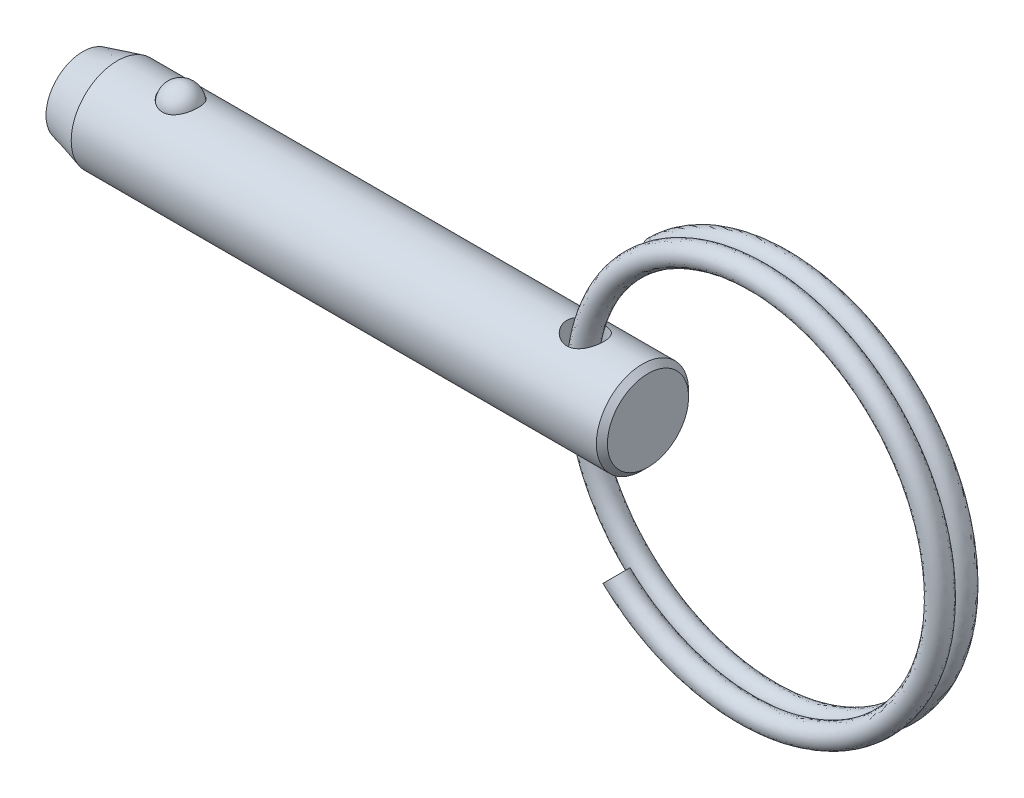
SolidWorks part; units mm, degrees
ref_plane "Front" through (0, 0, 0) normal (0, 0, 1) x (1, 0, 0)
ref_plane "Top" through (0, 0, 0) normal (0, 1, 0) x (1, 0, 0)
ref_plane "Right" through (0, 0, 0) normal (1, 0, 0) x (0, 0, -1)
sketch "Sketch1" plane through (0, 0, 0) normal (0, 0, 1) x (1, 0, 0)
  line L0 (19.4564, 2.794) -> (19.0754, 3.175)
  line L1 (19.0754, 3.175) -> (19.4564, 3.175) construction
  line L4 (19.4564, 2.794) -> (19.4564, 0)
  line L5 (19.4564, 3.175) -> (19.4564, 2.794) construction
  line L16 (19.0754, 3.175) -> (-17.0865, 3.175)
  line L17 (-19.4564, 3.175) -> (-19.4564, 2.54) construction
  line L19 (-17.0865, 3.175) -> (-19.4564, 3.175) construction
  line L22 (-19.4564, -3.175) -> (-17.0865, -3.175) construction
  line L23 (-12.7219, 2.8575) -> (-12.7219, -2.8575) construction
  line L24 (-19.4564, 0) -> (19.4564, 0)
  line L27 (19.4564, 0) -> (22.2504, 0) construction
  line L29 (-19.4564, 0) -> (-19.4564, -2.54) construction
  line L36 (13.8684, 0) -> (13.8684, 3.175) construction
  line L37 (-19.4564, 2.54) -> (-19.4564, 0)
  line L38 (-17.0865, -3.175) -> (19.4564, -3.175) construction
  line L39 (-19.4564, -2.54) -> (-19.4564, -3.175) construction
  line L40 (-17.0865, 3.175) -> (-19.4564, 2.54)
  line L42 (-17.0865, -3.175) -> (-19.4564, -2.54) construction
  line L43 (-17.0865, 3.175) -> (-17.0865, -3.175) construction
  circle A2 centre (-12.7219, 2.8575) radius 1.2319 construction
  point P35 (-11.5316, 3.175)
  dimension "A1" = 15
revolve "Revolve1" add sketch "Sketch1" angle 360 about L27
sketch "Sketch2" plane through (0, 0, 0) normal (0, 0, 1) x (1, 0, 0)
  line L0 (-11.4646, 2.8575) -> (-13.9792, 2.8575)
  line L1 (-12.7219, 4.0894) -> (-12.7219, 4.1148) construction
  line L2 (-11.4646, 2.8575) -> (-8.95, 2.8575) construction
  circle A0 centre (-12.7219, 2.8575) radius 1.2319 construction
  circle A1 centre (-12.7219, 2.8575) radius 1.2319 construction
  arc A2 (-13.9792, 2.8575) -> (-11.4646, 2.8575) centre (-12.7219, 2.8575) cw
  dimension "D1" = 0.0254
revolve "Cut-Revolve1" cut sketch "Sketch2" angle 360 about L2
sketch "Sketch3" plane through (0, 0, 0) normal (0, 0, 1) x (1, 0, 0)
  line L0 (-11.49, 2.8575) -> (-13.9538, 2.8575)
  line L1 (-11.49, 2.8575) -> (-9.0262, 2.8575) construction
  circle A0 centre (-12.7219, 2.8575) radius 1.2319 construction
  arc A1 (-11.49, 2.8575) -> (-13.9538, 2.8575) centre (-12.7219, 2.8575) ccw
revolve "Revolve2" add sketch "Sketch3" angle 360 about L1
sketch "Sketch4" plane through (0, 0, 0) normal (0, 0, 1) x (1, 0, 0)
  line L1 (15.1384, -3.175) -> (16.4084, -3.175)
  line L2 (15.1384, -3.175) -> (15.1384, 3.175)
  line L3 (15.1384, 3.175) -> (16.4084, 3.175)
  line L4 (16.4084, -3.175) -> (16.4084, 3.175)
  line L5 (15.1384, -3.175) -> (15.1384, -4.445) construction
  line L6 (16.4084, 3.175) -> (19.4564, 3.175) construction
  line L8 (13.8684, -3.175) -> (13.8684, 3.175) construction
  line L9 (13.8684, 0) -> (15.1384, 0) construction
  line L11 (15.1384, 0) -> (16.4084, 0) construction
  line L12 (19.0754, 3.175) -> (-17.0865, 3.175) construction
  line L14 (-17.0865, -3.175) -> (19.4564, -3.175) construction
  dimension "D1" = 2.54
revolve "Cut-Revolve2" cut sketch "Sketch4" angle 360 about L2
sketch "Sketch5" plane through (0, 0, 0) normal (0, 0, 1) x (1, 0, 0)
  line L0 (0, 0) -> (14.1614, 0) construction
  line L1 (14.1614, 0) -> (14.1614, 3.175) construction
  line L2 (19.0754, 3.175) -> (-17.0865, 3.175) construction
  line L3 (27.6234, 0) -> (41.0854, 0) construction
  line L4 (16.4084, 3.175) -> (16.1154, 3.175) construction
  line L5 (15.1384, 3.175) -> (16.4084, 3.175) construction
  line L6 (14.5412, 3.175) -> (14.5412, -3.175) construction
  line L7 (14.1614, 3.175) -> (13.8684, 3.175) construction
  line L8 (15.1384, -3.175) -> (16.4084, -3.175) construction
  line L9 (14.5412, -3.175) -> (16.4084, -3.175) construction
  line L10 (14.1614, 0) -> (27.6234, 0) construction
  line L12 (16.1154, 3.175) -> (14.5412, 3.175) construction
  line L13 (27.6234, 11.938) -> (27.6234, 13.462) construction
  circle A0 centre (27.6234, 0) radius 13.462
  circle A1 centre (27.6234, 0) radius 11.938 construction
  circle A2 centre (27.6234, 0) radius 12.7 construction
  point P26 (27.6234, 12.7)
curve "Helix/Spiral1" pitch 1.5494 height 1.3557 radius 13.462 left hand yes centre (27.6234, 0, 0) axis (0, 0, -1) start towards (1, 0, 0)
sketch "Sketch6" plane through (114.0038, 0, 0) normal (0, 1, 0) x (0, 0, -1)
  line L0 (0, 98.3184) -> (0, 99.0804) construction
  line L1 (0, 99.0804) -> (0, 99.8424) construction
  circle A0 centre (0, 99.0804) radius 0.762
  dimension "D1" = 1.524
sketch "Sketch7" plane through (0, 0, 0) normal (0, 0, 1) x (1, 0, 0)
  circle A0 centre (27.6234, 0) radius 13.462 construction
  circle A1 centre (27.6234, 0) radius 13.462
curve "Helix/Spiral2" pitch 1.5494 height 1.3557 radius 13.462 left hand yes centre (27.6234, 0, 0) axis (0, 0, 1) start towards (1, 0, 0)
sweep "Sweep1" add profiles "Sketch6" path "Helix/Spiral1"
sweep "Sweep2" add profiles "Sketch6<2>" path "Helix/Spiral2"
sketch "Sketch6<2>" plane through (114.0038, 0, 0) normal (0, 1, 0) x (0, 0, -1) same geometry as "Sketch6"
equation "\"D12@Sketch1\"=\"A@Sketch1\" * 0.80"
equation "\"D2@Sketch1\"=\"A@Sketch1\" * 0.9"
equation "\"D1@Sketch4\" = \"A@Sketch1\" / 2.5"
equation "\"Ring OD@Sketch5\" = \"R Ring Dia@Sketch5\" * 0.06"
equation "\"D4@Helix/Spiral1\"=\"Ring OD@Sketch5\" + 0.001"
equation "\"D1@Sketch6\"=\"Ring OD@Sketch5\""
equation "\"D4@Helix/Spiral2\" = \"D4@Helix/Spiral1\""
equation "\"D5@Helix/Spiral2\" = \"D5@Helix/Spiral1\""
